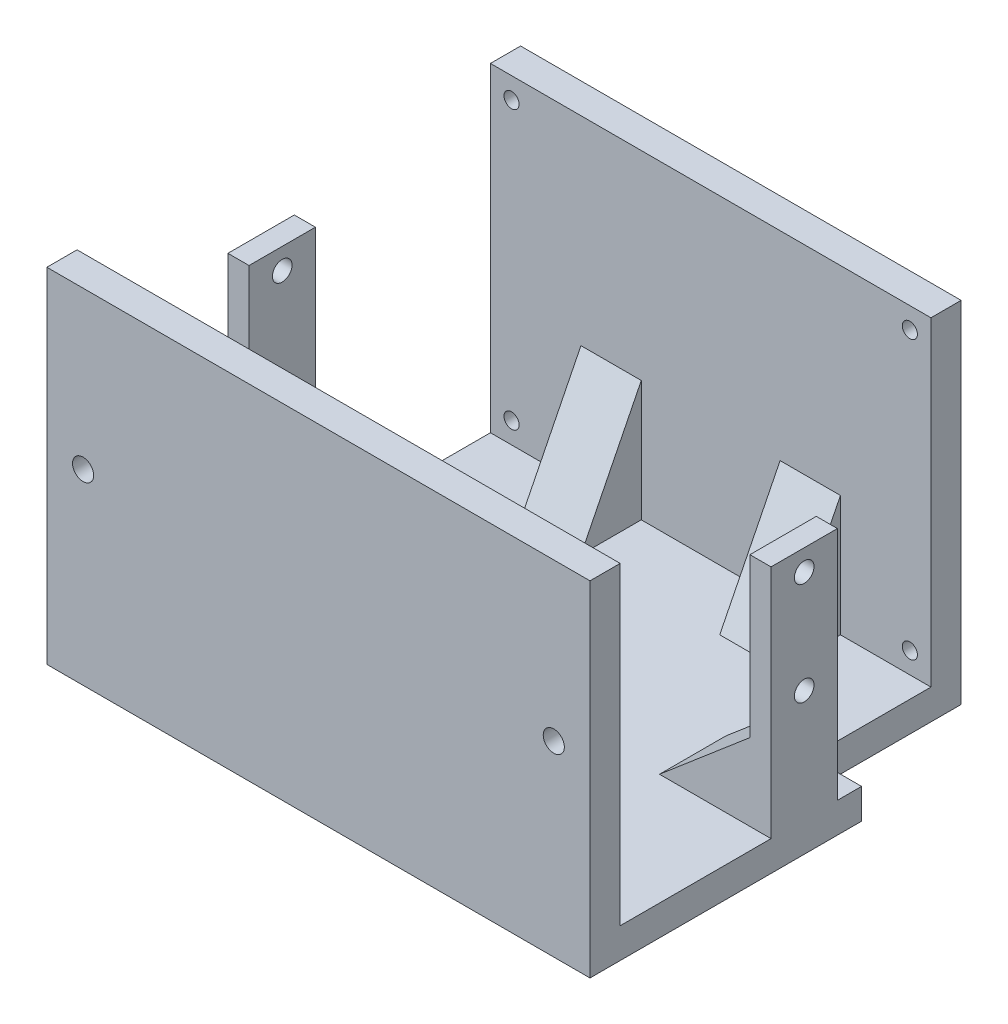
SolidWorks part; units mm, degrees
other "Annotazione1"
sketch "Schizzo3" plane through (-60, 53, -35) normal (-0.9097, 0.0412, -0.4133) x (0.357, 0.586, -0.7275)
material "PLA"
ref_plane "Piano frontale" through (0, 0, 0) normal (0, 0, 1) x (1, 0, 0)
ref_plane "Piano superiore" through (0, 0, 0) normal (0, 1, 0) x (1, 0, 0)
ref_plane "Piano destro" through (0, 0, 0) normal (1, 0, 0) x (0, 0, -1)
sketch "Schizzo1" plane through (0, 0, 0) normal (0, 1, 0) x (1, 0, 0)
  line L0 (36.5, -35) -> (45, -35)
  line L1 (-36.5, 35) -> (36.5, 35)
  line L2 (-36.5, 35) -> (-36.5, -35)
  line L3 (-36.5, -35) -> (36.5, -35)
  line L4 (36.5, 35) -> (36.5, -35)
  line L5 (-36.5, 35) -> (36.5, -35) construction
  line L6 (-36.5, -35) -> (36.5, 35) construction
  line L7 (45, -35) -> (45, 10)
  line L8 (45, 10) -> (36.5, 10)
  line L9 (36.5, 10) -> (36.5, -35)
  line L10 (0, 54.3826) -> (0, -65.8614) construction
  line L11 (-36.5, 10) -> (-36.5, -35)
  line L12 (-45, 10) -> (-36.5, 10)
  line L13 (-45, -35) -> (-45, 10)
  line L14 (-36.5, -35) -> (-45, -35)
  line L16 (41.5, 6) -> (45, 6)
  line L17 (41.5, 6) -> (41.5, -5)
  line L18 (41.5, -5) -> (45, -5)
  line L19 (45, 6) -> (45, -5)
  line L23 (45, 6) -> (45, -5)
  line L24 (-45, 6) -> (-45, -5)
  line L27 (-41.5, -5) -> (-45, -5)
  line L28 (-45, 6) -> (-45, -5)
  line L29 (-41.5, 6) -> (-45, 6)
  line L30 (-41.5, 6) -> (-41.5, -5)
  point P0 (0, 0)
  dimension "D1" = 73
  dimension "D2" = 70
  dimension "D3" = 8.5
  dimension "D4" = 45
  dimension "D5" = 4
  dimension "D6" = 11
  dimension "D7" = 3.5
extrude "Estrusione-Estrusione1" add sketch "Schizzo1" along normal blind 5 contours L4 L1 L2 L11 L3 L9 | L29 L2 L12 L13 L14 L11 L27 L28 | L7 L8 L4 L16 L19 L18 L0 region at (40.4702, 0, 13.9549) region at (0, 0, 0) region at (-40.4702, 0, 13.9549)
sketch "Schizzo2" plane through (0, 5, 0) normal (0, 1, 0) x (1, 0, 0)
  line L0 (-45, -35) -> (-45, -5) construction
  line L10 (-36.5, 35) -> (36.5, 35)
  line L11 (-36.5, 35) -> (-36.5, 30)
  line L12 (-36.5, 30) -> (36.5, 30)
  line L13 (36.5, 35) -> (36.5, 30)
  line L14 (-65.787, 0) -> (74.857, 0) construction
  line L15 (-45, -30) -> (45, -30)
  line L16 (45, -35) -> (45, -30)
  line L17 (-45, -35) -> (45, -35)
  line L18 (-45, -35) -> (-45, -30)
  line L19 (45, -35) -> (45, -5) construction
  line L20 (36.5, 35) -> (36.5, 10) construction
  line M18 (36.5, 10) -> (36.5, 35)
  line M27 (36.5, 35) -> (-36.5, 35)
  line M28 (-36.5, 35) -> (-36.5, 10)
  line M34 (-45, -5) -> (-45, -35)
  line M35 (-45, -35) -> (45, -35)
  line M36 (45, -35) -> (45, -5)
  dimension "D1" = 5
  dimension "D2" = 5
extrude "Estrusione-Estrusione2" add sketch "Schizzo2" along normal blind 53 contours L12 M28 M18 M27 region at (0, 5, -32.5)
sketch "Schizzo4" plane through (0, 0, -35) normal (0, 0, -1) x (-1, 0, 0)
  line L0 (0, 58.3333) -> (0, -3.2969) construction
  line L1 (-36.5, 58) -> (36.5, 58) construction
  line L2 (-43.3221, 31.5) -> (46.5564, 31.5) construction
  circle A0 centre (-33, 54.5) radius 1.25
  circle A1 centre (33, 54.5) radius 1.25
  circle A2 centre (33, 8.5) radius 1.25
  circle A3 centre (-33, 8.5) radius 1.25
  dimension "D3" = 2.5
  dimension "D1" = 66
  dimension "D2" = 46
  dimension "D4" = 26.5
extrude "Taglio-Estrusione1" cut sketch "Schizzo4" against normal blind 10
extrude "Estrusione-Estrusione3" add sketch "Schizzo1<3>" along normal blind 44 contours L30 L29 L13 L27 | L17 L18 L7 L16 region at (43.25, 0, -0.5) region at (-43.25, 0, -0.5)
sketch "Schizzo1<3>" plane through (0, 0, 0) normal (0, 1, 0) x (1, 0, 0) same geometry as "Schizzo1"
sketch "Schizzo5" plane through (-45, 0, 0) normal (-1, 0, 0) x (0, 0, 1)
  line L1 (-0.5, -5.2786) -> (-0.5, 51.5349) construction
  line L5 (5, 44) -> (-6, 44) construction
  circle A0 centre (-0.5, 40.5) radius 1.625
  circle A1 centre (-0.5, 23.5) radius 1.625
  point P8 (-0.5, 44)
  dimension "D2" = 3.25
  dimension "D3" = 17
  dimension "D1" = 3.5
extrude "Taglio-Estrusione2" cut sketch "Schizzo5" against normal through all
extrude "Estrusione-Estrusione4" add sketch "Schizzo2<3>" along normal blind 52 contours L15 M34 M35 M36 region at (0, 5, 32.5)
sketch "Schizzo2<3>" plane through (0, 5, 0) normal (0, 1, 0) x (1, 0, 0) same geometry as "Schizzo2"
sketch "Schizzo8" plane through (0, 0, 30) normal (0, 0, -1) x (-1, 0, 0)
  line L0 (45, 31) -> (-54.6669, 31) construction
  line L1 (45, 57) -> (45, 5) construction
  line L2 (0, 61.8795) -> (0, -15.2821) construction
  circle A0 centre (-39, 31) radius 1.75
  circle A2 centre (39, 31) radius 1.75
  dimension "D2" = 3.5
  dimension "D1" = 39
extrude "Taglio-Estrusione3" cut sketch "Schizzo8" against normal through all
sketch "Schizzo11" plane through (0, 0, 5) normal (0, 0, 1) x (1, 0, 0)
  line L0 (-41.5, 5) -> (-41.5, 17.748)
  line L1 (-41.5, 44) -> (-41.5, 5) construction
  line L2 (-41.5, 17.748) -> (-26.5154, 5)
  line L3 (-36.5, 5) -> (36.5, 5) construction
  line L4 (-26.5154, 5) -> (-41.5, 5)
  line L5 (0, 58.9964) -> (0, -12.0118) construction
  line L6 (41.5, 17.748) -> (26.5154, 5)
  line L7 (41.5, 5) -> (41.5, 17.748)
  line L8 (26.5154, 5) -> (41.5, 5)
extrude "Estrusione-Estrusione5" add sketch "Schizzo11" against normal blind 11 contours L6 L8 L7 | L4 L0 L2 region at (36.5051, 9.2493, 5)
ref_plane "Piano1" through (-16.5, 0, 0) normal (-1, 0, 0) x (0, 0, 1)
sketch "Schizzo13" plane through (-16.5, 0, 0) normal (-1, 0, 0) x (0, 0, 1)
  line L0 (-30, 25) -> (-20, 5)
  line L1 (-30, 58) -> (-30, 5) construction
  line L2 (-30, 5) -> (-10, 5) construction
  line L3 (-20, 5) -> (-30, 5)
  line L4 (-30, 5) -> (-30, 25)
  dimension "D1" = 10
  dimension "D2" = 20
extrude "Estrusione-Estrusione6" add sketch "Schizzo13" along normal blind 5 and the other way blind 5
mirror "Specchia1" about plane through (0, 0, 0) normal (1, 0, 0) of "Estrusione-Estrusione6"
sketch "Schizzo14" plane through (0, 0, 35) normal (0, 0, 1) x (1, 0, 0)
  line L0 (-45, 33.972) -> (45, 33.972)
  line L1 (-45, 57) -> (-45, 0) construction
  line L2 (45, 57) -> (45, 0) construction
  line L3 (45, 33.972) -> (45, 25.0792)
  line L4 (45, 25.0792) -> (-45, 25.125)
  line L5 (-45, 33.972) -> (-45, 25.125)
sketch "Schizzo15" plane through (-45, 0, 0) normal (-1, 0, 0) x (0, 0, 1)
  line L1 (-7.3064, 46.4415) -> (6.2905, 46.4415)
  line L2 (-7.3064, 46.4415) -> (-7.3064, 18.5445)
  line L3 (-7.3064, 18.5445) -> (6.2905, 18.5445)
  line L4 (6.2905, 46.4415) -> (6.2905, 18.5445)
  line L5 (-7.3064, 46.4415) -> (6.2905, 18.5445) construction
  line L6 (-7.3064, 18.5445) -> (6.2905, 46.4415) construction
  point P0 (-0.5079, 32.493)
extrude "Taglio-Estrusione5" [suppressed] cut sketch "Schizzo15" against normal through all both and the other way through all flip side to cut
